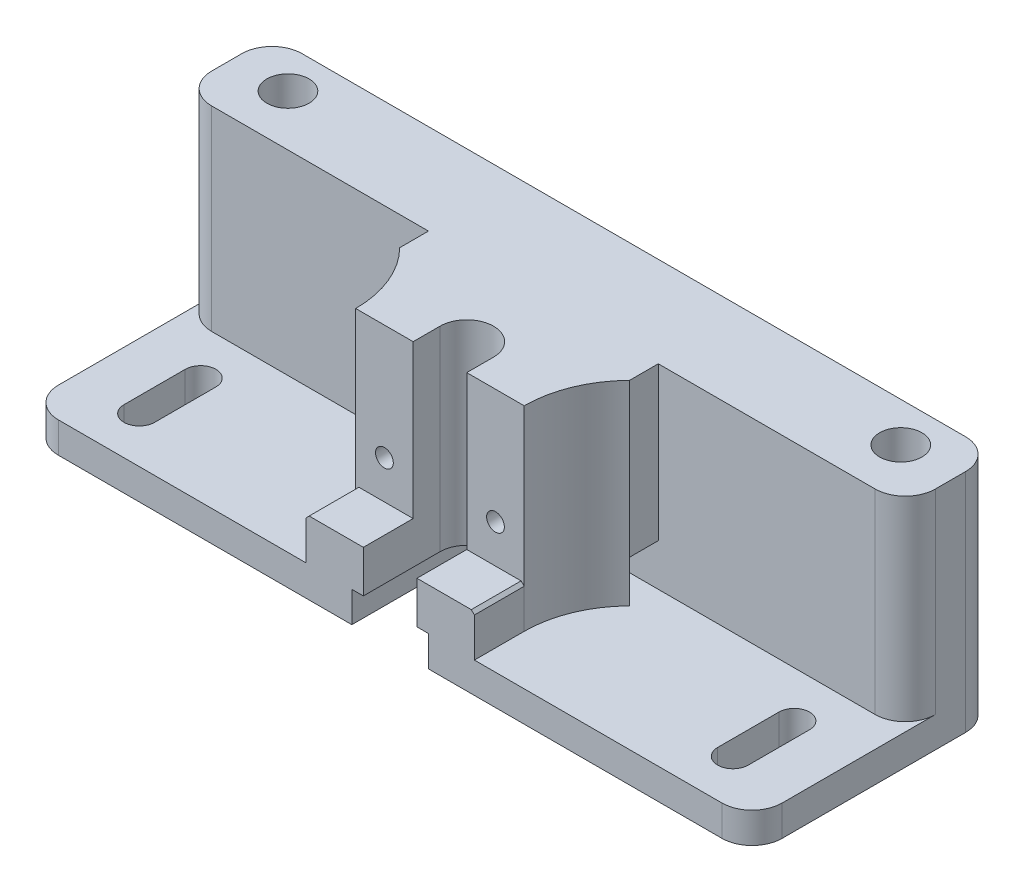
SolidWorks part; units mm, degrees
ref_plane "Front Plane" through (0, 0, 0) normal (0, 0, 1) x (1, 0, 0)
ref_plane "Top Plane" through (0, 0, 0) normal (0, 1, 0) x (1, 0, 0)
ref_plane "Right Plane" through (0, 0, 0) normal (1, 0, 0) x (0, 0, -1)
ref_plane "Plane1" through (0, 0, -20.6375) normal (0, 0, -1) x (-1, 0, 0)
sketch "Sketch1" plane through (0, 0, -20.6375) normal (0, 0, -1) x (-1, 0, 0)
  line L0 (19.05, 0) -> (19.05, 25.4)
  line L1 (19.05, 25.4) -> (-19.05, 25.4)
  line L2 (-19.05, 25.4) -> (-19.05, 0)
  line L3 (-19.05, 0) -> (19.05, 0)
extrude "Boss-Extrude1" add sketch "Sketch1" against normal blind 25.0825
ref_plane "Plane2" through (0, 0, -2.2225) normal (0, 0, 1) x (1, 0, 0)
sketch "Sketch6" plane through (0, 0, -2.2225) normal (0, 0, 1) x (1, 0, 0)
  line L0 (-6.0325, 8.1831) -> (-9.2075, 10.0162)
  line L1 (-9.2075, 10.0162) -> (-12.3825, 8.1831)
  line L2 (-12.3825, 8.1831) -> (-12.3825, 4.5169)
  line L3 (-12.3825, 4.5169) -> (-9.2075, 2.6838)
  line L4 (-9.2075, 2.6838) -> (-6.0325, 4.5169)
  line L5 (-6.0325, 4.5169) -> (-6.0325, 8.1831)
extrude "Cut-Extrude1" cut sketch "Sketch6" against normal blind 2.3876
sketch "Sketch12" plane through (0, 0, -2.2225) normal (0, 0, 1) x (1, 0, 0)
  line L0 (6.0325, 8.1831) -> (6.0325, 4.5169)
  line L1 (6.0325, 4.5169) -> (9.2075, 2.6838)
  line L2 (9.2075, 2.6838) -> (12.3825, 4.5169)
  line L3 (12.3825, 4.5169) -> (12.3825, 8.1831)
  line L4 (12.3825, 8.1831) -> (9.2075, 10.0162)
  line L5 (9.2075, 10.0162) -> (6.0325, 8.1831)
extrude "Cut-Extrude2" cut sketch "Sketch12" against normal blind 2.3876
ref_plane "Plane3" through (0, 0, 0) normal (0, -1, 0) x (-1, 0, 0)
sketch "Sketch18" plane through (0, 0, 0) normal (0, -1, 0) x (-1, 0, 0)
  line L0 (13.97, -4.445) -> (19.05, -4.445)
  line L1 (19.05, -4.445) -> (19.05, 7.9375)
  arc A0 (19.05, 7.9375) -> (13.97, -4.445) centre (31.6012, -4.445) ccw
extrude "Cut-Extrude3" cut sketch "Sketch18" against normal through all
sketch "Sketch19" plane through (0, 0, 0) normal (0, -1, 0) x (1, 0, 0)
  line L0 (4.445, 4.445) -> (-4.445, 4.445)
  line L1 (-4.445, 4.445) -> (-4.445, 0)
  line L2 (4.445, 0) -> (4.445, 4.445)
  arc A0 (-4.445, 0) -> (4.445, 0) centre (0, 0) ccw
extrude "Cut-Extrude4" cut sketch "Sketch19" against normal through all
sketch "Sketch20" plane through (0, 0, 0) normal (0, -1, 0) x (1, 0, 0)
  line L0 (19.05, -7.9375) -> (19.05, 4.445)
  line L1 (19.05, 4.445) -> (13.97, 4.445)
  arc A0 (13.97, 4.445) -> (19.05, -7.9375) centre (31.6012, 4.445) ccw
extrude "Cut-Extrude5" cut sketch "Sketch20" against normal through all
sketch "Sketch21" plane through (0, 0, 0) normal (0, -1, 0) x (1, 0, 0)
  line L0 (4.445, 0) -> (4.445, 12.7)
  line L1 (4.445, 12.7) -> (13.97, 12.7)
  line L2 (13.97, 12.7) -> (13.97, 4.445)
  line L3 (19.05, -7.9375) -> (-19.05, -7.9375)
  line L4 (-13.97, 4.445) -> (-13.97, 12.7)
  line L5 (-13.97, 12.7) -> (-4.445, 12.7)
  line L6 (-4.445, 12.7) -> (-4.445, 0)
  arc A0 (13.97, 4.445) -> (19.05, -7.9375) centre (31.6012, 4.445) ccw
  arc A1 (-19.05, -7.9375) -> (-13.97, 4.445) centre (-31.6012, 4.445) ccw
  arc A2 (-4.445, 0) -> (4.445, 0) centre (0, 0) ccw
extrude "Boss-Extrude2" add sketch "Sketch21" along normal blind 6.985
sketch "Sketch22" plane through (0, -6.985, 0) normal (0, -1, 0) x (1, 0, 0)
  line L0 (-4.445, -6.35) -> (4.445, -6.35)
  line L1 (4.445, -6.35) -> (4.445, 12.7)
  line L2 (4.445, 12.7) -> (60, 12.7)
  line L3 (60, 12.7) -> (60, -12.7)
  line L4 (60, -12.7) -> (-60, -12.7)
  line L5 (-60, -12.7) -> (-60, 12.7)
  line L6 (-60, 12.7) -> (-4.445, 12.7)
  line L7 (-4.445, 12.7) -> (-4.445, -6.35)
  point P8 (0, -12.7)
  dimension "D1" = 25.4
  dimension "D2" = 120
  dimension "D3" = 8.89
  dimension "D4" = 4.445
extrude "Boss-Extrude3" add sketch "Sketch22" along normal blind 5.08
ref_plane "Plane4" through (4.445, 0, 0) normal (-1, 0, 0) x (0, 0, 1)
sketch "Sketch29" plane through (4.445, 0, 0) normal (-1, 0, 0) x (0, 0, 1)
  line L0 (12.7, -6.985) -> (-6.35, -6.985)
  line L1 (-6.35, -6.985) -> (-6.35, -12.065)
  line L2 (-6.35, -12.065) -> (12.7, -12.065)
  line L3 (12.7, -12.065) -> (12.7, -6.985)
extrude "Cut-Extrude6" cut sketch "Sketch29" against normal blind 1.905
sketch "Sketch30" plane through (-4.445, 0, 0) normal (1, 0, 0) x (0, 0, -1)
  line L0 (-12.7, -6.985) -> (-12.7, -12.065)
  line L1 (-12.7, -12.065) -> (6.35, -12.065)
  line L2 (6.35, -12.065) -> (6.35, -6.985)
  line L3 (6.35, -6.985) -> (-12.7, -6.985)
extrude "Cut-Extrude7" cut sketch "Sketch30" against normal blind 1.905
ref_plane "Plane5" through (0, -12.065, 0) normal (0, -1, 0) x (-1, 0, 0)
sketch "Sketch48" plane through (0, -12.065, 0) normal (0, -1, 0) x (-1, 0, 0)
  line L0 (-51.7525, 5.08) -> (-51.7525, -5.08)
  line L1 (-46.6725, -5.08) -> (-46.6725, 5.08)
  arc A0 (-46.6725, 5.08) -> (-51.7525, 5.08) centre (-49.2125, 5.08) ccw
  arc A1 (-51.7525, -5.08) -> (-46.6725, -5.08) centre (-49.2125, -5.08) ccw
extrude "Cut-Extrude10" cut sketch "Sketch48" against normal up to next
sketch "Sketch57" plane through (0, -12.065, 0) normal (0, -1, 0) x (-1, 0, 0)
  line L0 (46.6725, 5.08) -> (46.6725, -5.08)
  line L1 (51.7525, -5.08) -> (51.7525, 5.08)
  arc A0 (51.7525, 5.08) -> (46.6725, 5.08) centre (49.2125, 5.08) ccw
  arc A1 (46.6725, -5.08) -> (51.7525, -5.08) centre (49.2125, -5.08) ccw
extrude "Cut-Extrude11" cut sketch "Sketch57" against normal up to next
ref_plane "Plane6" through (0, 6.35, 0) normal (0, 1, 0) x (1, 0, 0)
sketch "Sketch67" plane through (0, 6.35, 0) normal (0, 1, 0) x (1, 0, 0)
  line L0 (-7.7343, 20.6375) -> (-9.2075, 20.6375)
  line L1 (-9.2075, 20.6375) -> (-9.2075, 4.6101)
  line L2 (-9.2075, 4.6101) -> (-7.7343, 4.6101)
  line L3 (-7.7343, 4.6101) -> (-7.7343, 20.6375)
  line L4 (-9.2075, 20.6375) -> (-9.2075, 4.6101) construction
revolve "Cut-Revolve1" cut sketch "Sketch67" angle 360 about L1 reverse direction yes
sketch "Sketch77" plane through (0, 6.35, 0) normal (0, 1, 0) x (1, 0, 0)
  line L0 (10.6807, 20.6375) -> (9.2075, 20.6375)
  line L1 (9.2075, 20.6375) -> (9.2075, 4.6101)
  line L2 (9.2075, 4.6101) -> (10.6807, 4.6101)
  line L3 (10.6807, 4.6101) -> (10.6807, 20.6375)
  line L4 (9.2075, 20.6375) -> (9.2075, 4.6101) construction
revolve "Cut-Revolve2" cut sketch "Sketch77" angle 360 about L1 reverse direction yes
hole_wizard "M2.5 Clearance Hole1" positions "Sketch79" profile "Sketch78" hole size "M2.5" standard "ANSI Metric"
sketch "Sketch79" plane through (0, 0, 4.445) normal (0, 0, 1) x (1, 0, 0)
  point P0 (9.2075, 6.35)
  point P1 (-9.2075, 6.35)
sketch "Sketch78" plane through (9.2075, 6.35, 4.445) normal (1, 0, 0) x (0, -1, 0)
  line L0 (0, 0) -> (0, 25.0825)
  line L1 (0, 25.0825) -> (1.4732, 25.0825)
  line L2 (1.4732, 25.0825) -> (1.4732, 0)
  line L5 (1.4732, 0) -> (0, 0)
  line L11 (0, -6.35) -> (0, 107.95) construction
  dimension "Thru Hole Dia." = 2.9464
  dimension "Thru Hole Depth" = 25.0825
chamfer "Chamfer1" distance 0.5111 angle 45.61 1 edges at (13.97, 0, 8.5725) first distance on face at (13.97, -3.4925, 8.5725)
chamfer "Chamfer2" distance 0.5582 angle 43.977 1 edges at (-13.97, 0, 8.5725) first distance on face at (-13.97, -3.4925, 8.5725)
sketch "Sketch80" plane through (0, 0, -20.6375) normal (0, 0, -1) x (-1, 0, 0)
  line L0 (-19.05, 25.4) -> (19.05, 25.4)
  line L1 (-19.05, 25.4) -> (-19.05, 0)
  line L2 (-19.05, 0) -> (19.05, 0)
  line L3 (19.05, 25.4) -> (19.05, 0)
extrude "Cut-Extrude13" cut sketch "Sketch80" against normal up to surface (7.9375 mm away) up to face at (0, -9.525, -12.7)
sketch "Sketch81" plane through (0, 25.4, 0) normal (0, 1, 0) x (1, 0, 0)
  line L0 (-19.05, 12.7) -> (19.05, 12.7) construction
  line L1 (60, 12.7) -> (-60, 12.7)
  line L2 (60, 12.7) -> (60, 27.7)
  line L3 (60, 27.7) -> (-60, 27.7)
  line L4 (-60, 12.7) -> (-60, 27.7)
  line L5 (-60, 12.7) -> (60, 12.7) construction
  point P0 (0, 12.7)
  point P7 (0, 12.7)
  dimension "D1" = 120
  dimension "D2" = 15
extrude "Boss-Extrude4" add sketch "Sketch81" against normal up to surface (37.465 mm away) up to face at (-49.2125, -12.065, 0)
sketch "Sketch82" plane through (0, -12.065, 0) normal (0, -1, 0) x (1, 0, 0)
  line L0 (-42.1371, -21.1564) -> (42.1371, -21.1564) construction
  circle A0 centre (-50.8, -21.1564) radius 3.5
  circle A1 centre (50.8, -21.1564) radius 3.5
  point P3 (0, -21.1564)
  point P7 (0, -21.1564)
  dimension "D1" = 50.8
  dimension "D3" = 7
  dimension "D4" = 7
  dimension "D2" = 50.8
extrude "Cut-Extrude14" cut sketch "Sketch82" against normal through all
fillet "Fillet3" radius 5 2 edges at (60, 6.6675, -27.7) (-60, 6.6675, -27.7)
fillet "Fillet4" radius 5 2 edges at (-60, 9.2075, -12.7) (60, 9.2075, -12.7)
fillet "Fillet5" radius 5 2 edges at (60, -9.525, 12.7) (-60, -9.525, 12.7)
